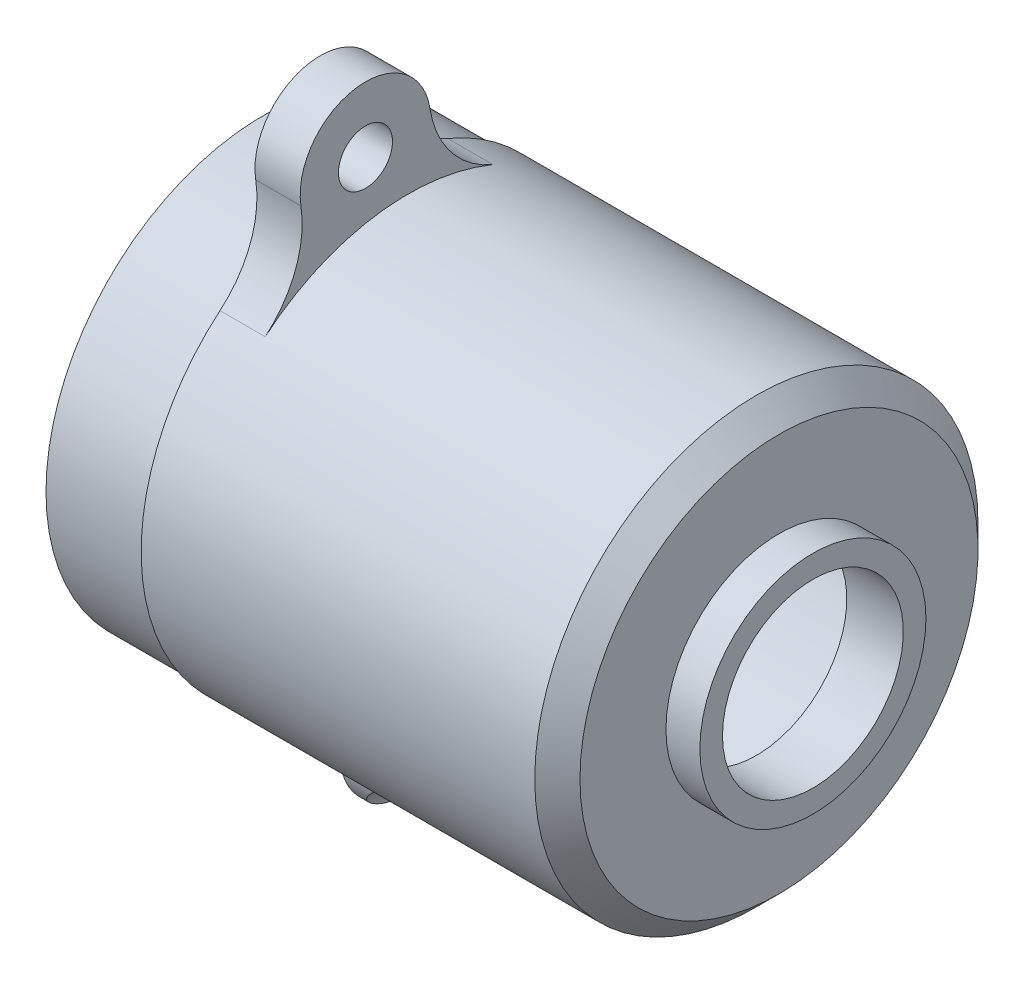
SolidWorks part; units mm, degrees
material "6061-T6 (SS)"
ref_plane "Front Plane" through (0, 0, 0) normal (0, 0, 1) x (1, 0, 0)
ref_plane "Top Plane" through (0, 0, 0) normal (0, 1, 0) x (1, 0, 0)
ref_plane "Right Plane" through (0, 0, 0) normal (1, 0, 0) x (0, 0, -1)
other "Center of Mass"
sketch "Sketch1" plane through (-31.75, 0, 0) normal (1, 0, 0) x (0, 0, -1)
  line L0 (0, 0) -> (-2.9885, 19.3009) construction
  line L1 (-0.1168, 15.7295) -> (1.5403, 20.0021) construction
  line L2 (1.5403, 20.0021) -> (-1.3314, 23.5735) construction
  line L3 (-1.3314, 23.5735) -> (-5.8601, 22.8723) construction
  line L4 (-5.8601, 22.8723) -> (-7.5172, 18.5996) construction
  line L5 (-7.5172, 18.5996) -> (-4.6456, 15.0282) construction
  line L6 (-4.6456, 15.0282) -> (-0.1168, 15.7295) construction
  line L7 (4.6456, -15.0282) -> (0.1168, -15.7295) construction
  line L8 (0.1168, -15.7295) -> (-1.5403, -20.0021) construction
  line L9 (-1.5403, -20.0021) -> (1.3314, -23.5735) construction
  line L10 (1.3314, -23.5735) -> (5.8601, -22.8723) construction
  line L11 (5.8601, -22.8723) -> (7.5172, -18.5996) construction
  line L12 (7.5172, -18.5996) -> (4.6456, -15.0282) construction
  line L13 (-7.5172, 18.5996) -> (1.5403, 20.0021) construction
  line L15 (0, 0) -> (12.0771, 1.87) construction
  circle A0 centre (0, 0) radius 13.9746
  circle A1 centre (0, 0) radius 15.5621 construction
  circle A3 centre (2.9885, -19.3009) radius 3.9688 construction
  circle A4 centre (-2.9885, 19.3009) radius 8.7404 construction
  arc A8 (-10.0273, 11.901) -> (-5.9586, -14.3762) centre (0, 0) ccw
  arc A9 (5.9586, 14.3762) -> (10.0273, -11.901) centre (0, 0) cw
  circle A16 centre (-2.9885, 19.3009) radius 2.667 construction
  circle A17 centre (2.9885, -19.3009) radius 2.667 construction
  arc A18 (-9.6776, 36.4316) -> (-11.5083, 22.6659) centre (127.0686, 11.2409) ccw construction
  arc A19 (4.4842, 36.4316) -> (4.6143, 28.807) centre (76.9988, 33.8561) ccw construction
  arc A20 (-10.0273, 11.901) -> (-7.5172, 18.5996) centre (-14.7303, 17.4828) ccw
  arc A21 (-7.5172, 18.5996) -> (1.5403, 20.0021) centre (-2.9885, 19.3009) cw
  arc A22 (1.5403, 20.0021) -> (5.9586, 14.3762) centre (8.7533, 21.1189) ccw
  arc A23 (7.5172, -18.5996) -> (10.0273, -11.901) centre (14.7303, -17.4828) cw
  arc A24 (-1.5403, -20.0021) -> (7.5172, -18.5996) centre (2.9885, -19.3009) ccw
  arc A25 (-5.9586, -14.3762) -> (-1.5403, -20.0021) centre (-8.7533, -21.1189) cw
  point P4 (-2.3812, 15.3788)
  dimension "D1" = 27.9492
  dimension "D4" = 5.334
  dimension "D2" = 1.5875
  dimension "D3" = 7.9375
extrude "Boss-Extrude1" add sketch "Sketch1" along normal blind 3.175
sketch "Sketch2" plane through (-28.575, 0, 0) normal (1, 0, 0) x (0, 0, -1)
  circle A0 centre (0, 0) radius 13.9746
  circle A1 centre (0, 0) radius 15.5621
  arc A2 (-10.0273, 11.901) -> (-5.9586, -14.3762) centre (0, 0) ccw construction
  circle A3 centre (0, 0) radius 13.9746 construction
extrude "Boss-Extrude2" add sketch "Sketch2" along normal up to surface (24.4625 mm away)
sketch "Sketch5" plane through (0, 0, 0) normal (0, 0, 1) x (1, 0, 0)
  line L1 (-0.1437, 7.9375) -> (-0.1437, 6.35)
  line L3 (-4.1125, -15.5621) -> (-4.1125, 15.5621) construction
  line L4 (-4.1125, 6.35) -> (-4.1125, 15.5621)
  line L5 (0, 0) -> (45.5597, 0) construction
  line L6 (-4.1125, 6.35) -> (-0.1437, 6.35)
  line L9 (-0.1437, 7.9375) -> (-2.525, 7.9375)
  line L10 (-2.525, 7.9375) -> (-2.525, 13.9746)
  line L11 (-2.525, 13.9746) -> (-4.1125, 15.5621)
  dimension "D2" = 3.9688
  dimension "D1" = 12.7
  dimension "D3" = 1.5875
  dimension "D4" = 1.5875
  dimension "D5" = 45
revolve "Revolve1" add sketch "Sketch5" angle 360 about L5
sketch "Sketch3" plane through (-31.75, 0, 0) normal (-1, 0, 0) x (0, 0, 1)
  circle A0 centre (0, 0) radius 13.9746
  circle A1 centre (0, 0) radius 15.2446
  circle A2 centre (0, 0) radius 13.9746 construction
  dimension "D1" = 1.27
extrude "Boss-Extrude3" add sketch "Sketch3" along normal blind 7
sketch "Sketch6" plane through (0, 0, 0) normal (0, 0, 1) x (1, 0, 0)
  line L0 (-31.75, -23.8836) -> (-31.5663, -23.8836)
  line L1 (-31.75, -23.8836) -> (-28.575, -23.8836) construction
  line L2 (-31.75, -23.8836) -> (-31.75, -25.4)
  line L3 (-31.75, -18.5996) -> (-31.75, -23.8836) construction
  arc A0 (-31.75, -25.4) -> (-31.3998, -27.4796) centre (-25.4, -25.4) ccw construction
  arc A1 (-31.5663, -23.8836) -> (-31.75, -25.4) centre (-25.4, -25.4) cw
extrude "Cut-Extrude1" cut sketch "Sketch6" against normal through all both and the other way through all
hole_wizard "#6 Clearance Hole1" positions "Sketch7" profile "Sketch8" hole size "#6" standard "ANSI Inch" end condition up to next
sketch "Sketch7" plane through (-28.575, 0, 0) normal (1, 0, 0) x (0, 0, -1)
  point P0 (-2.9885, 19.3009)
  point P3 (2.9885, -19.3009)
sketch "Sketch8" plane through (-28.575, 19.3009, 2.9885) normal (0, 1, 0) x (0, 0, -1)
  line L0 (0, 0) -> (0, 3.175)
  line L1 (0, 3.175) -> (1.8986, 3.175)
  line L2 (1.8986, 3.175) -> (1.8986, 0)
  line L5 (1.8986, 0) -> (0, 0)
  line L11 (0, -6.35) -> (0, 107.95) construction
  dimension "Thru Hole Dia." = 3.7973
  dimension "Thru Hole Depth" = 3.175
equation "\"motor diameter\"= 28mm"
equation "\"D1@Sketch1\"=\"motor diameter\"-0.002in"
equation "\"D1@Boss-Extrude3\"=7mm"
equation "\"D2@Sketch5\"=5/32"
